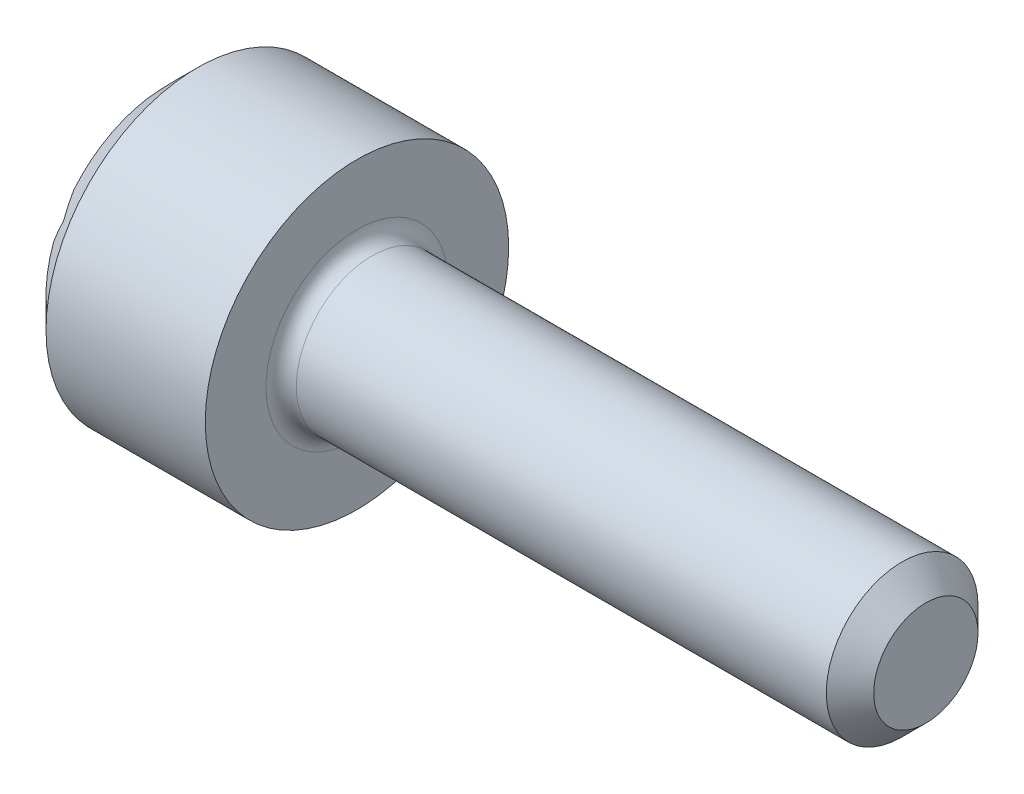
SolidWorks part; units mm, degrees
material "NA"
ref_plane "Front Plane" through (0, 0, 0) normal (0, 0, 1) x (1, 0, 0)
ref_plane "Top Plane" through (0, 0, 0) normal (0, 1, 0) x (1, 0, 0)
ref_plane "Right Plane" through (0, 0, 0) normal (1, 0, 0) x (0, 0, -1)
sketch "Sketch1" plane through (0, 0, 0) normal (0, 1, 0) x (1, 0, 0)
  line L0 (0, 0) -> (0, 4)
  line L1 (0, 4) -> (5, 4)
  line L2 (5, 4) -> (5, 2)
  line L3 (5, 2) -> (20, 2)
  line L4 (20, 2) -> (20, 0)
  line L5 (20, 0) -> (0, 0)
  point P3 (5, 2)
  dimension "16" = 5
  dimension "D2" = 4
  dimension "D3" = 2
  dimension "20" = 15
revolve "Revolve1" add sketch "Sketch1" angle 360 about L5
chamfer "Chamfer1" distance 0.625 angle 45 1 edges at (20, 0, -2)
sketch "Sketch3" plane through (0, 0, 0) normal (0, 1, 0) x (1, 0, 0)
  line L0 (0, 0) -> (5.7321, 0)
  line L1 (0, 4) -> (0, -4) construction
  line L2 (5.7321, 0) -> (4, 3)
  line L3 (4, 3) -> (0, 3)
  line L4 (0, 3) -> (0, 0)
  dimension "5" = 3
  dimension "D2" = 4
  dimension "D3" = 60
revolve "Cut-Revolve1" cut sketch "Sketch3" angle 360 about L0
sketch "Sketch2" plane through (0, 0, 0) normal (-1, 0, 0) x (0, 0, 1)
  line L0 (0, 0) -> (0, 3.4641) construction
  line L1 (0, 3.4641) -> (-3, 1.7321)
  line L2 (-3, 1.7321) -> (-3, -1.7321)
  line L3 (-3, -1.7321) -> (0, -3.4641)
  line L4 (0, -3.4641) -> (3, -1.7321)
  line L5 (3, -1.7321) -> (3, 1.7321)
  line L6 (3, 1.7321) -> (0, 3.4641)
  circle A0 centre (0, 0) radius 3 construction
  dimension "4" = 6
extrude "Cut-Extrude1" cut sketch "Sketch2" against normal blind 4 contours L4 L5 L6 L1 L2 L3
chamfer "Chamfer2" distance 0.8 angle 45 1 edges at (0, 0, -4)
fillet "Fillet1" radius 0.4 1 edges at (5, 0, -2)
ref_plane "Plane1" through (21.6, 0, 0) normal (1, 0, 0) x (0, 0, -1)
sketch "Sketch5" plane through (21.6, 0, 0) normal (1, 0, 0) x (0, 0, -1)
  circle A0 centre (0, 0) radius 4
  dimension "D1" = 8
curve "Helix/Spiral1" pitch 1.25 height 30 turns 24
sketch "Sketch6" plane through (0, 0, 0) normal (0, 0, 1) x (1, 0, 0)
  line L0 (20.9873, 4.1353) -> (21.6, 3.0524) construction
  line L1 (21.6, 3.0524) -> (22.2127, 4.1353) construction
  line L2 (22.2127, 4.1353) -> (20.9873, 4.1353) construction
  line L3 (21.6, 4.1353) -> (21.6, 3.0524) construction
  line L4 (21.0639, 4) -> (22.1361, 4)
  line L5 (21.0639, 4) -> (21.4469, 3.323)
  line L6 (21.7531, 3.323) -> (22.1361, 4)
  line L7 (21.7531, 3.323) -> (21.4469, 3.323)
  point P6 (21.6, 4)
  dimension "D1" = 59
  dimension "D2" = 0.677
  dimension "D3" = 0.1353
  dimension "D4" = 0.2706
sweep "Cut-Sweep2" [suppressed] cut profiles "Sketch6" path "Helix/Spiral1"
